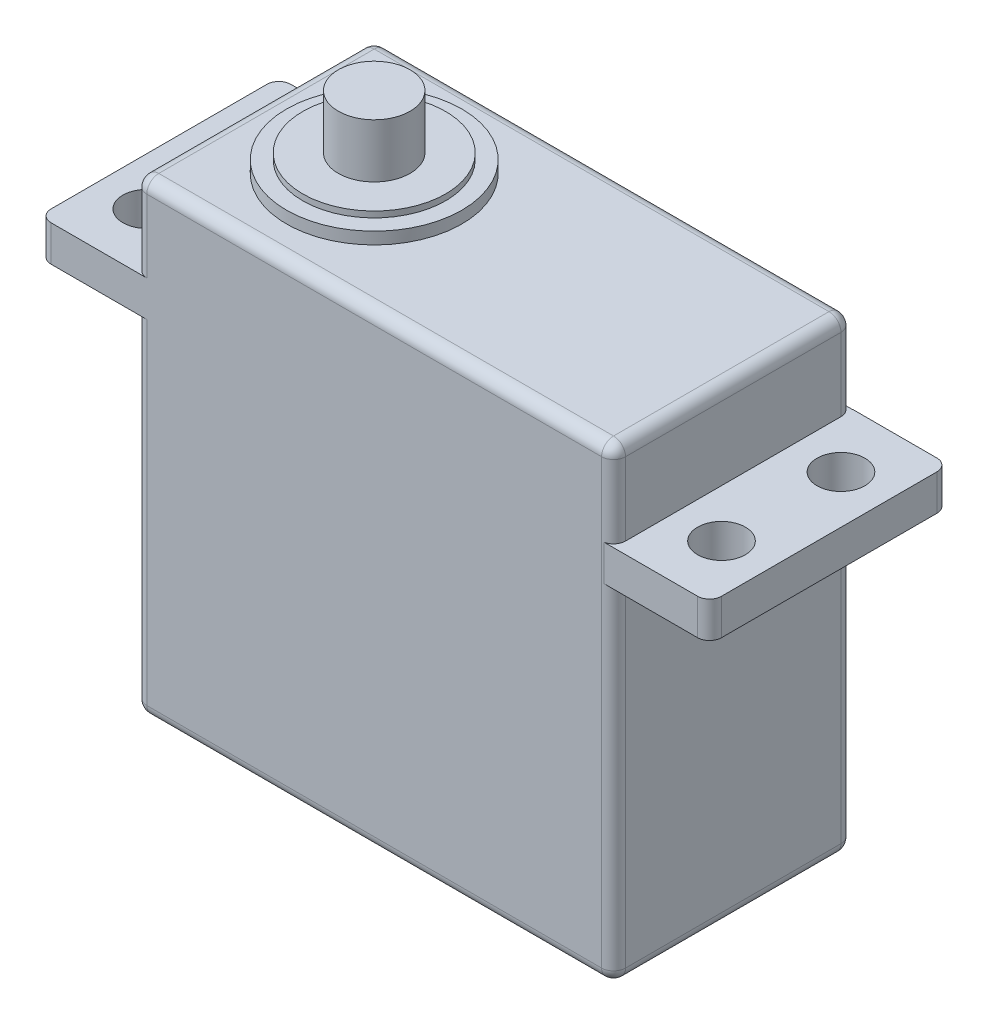
SolidWorks part; units mm, degrees
ref_plane "前视基准面" through (0, 0, 0) normal (0, 0, 1) x (1, 0, 0)
ref_plane "上视基准面" through (0, 0, 0) normal (0, 1, 0) x (1, 0, 0)
ref_plane "右视基准面" through (0, 0, 0) normal (1, 0, 0) x (0, 0, -1)
other "Configuration Table"
sketch "草图1" plane through (0, 0, 0) normal (0, 0, 1) x (1, 0, 0)
  line L1 (-23.1016, 36.7005) -> (16.8984, 36.7005)
  line L2 (-23.1016, 36.7005) -> (-23.1016, -2.2995)
  line L3 (-23.1016, -2.2995) -> (16.8984, -2.2995)
  line L4 (16.8984, 36.7005) -> (16.8984, -2.2995)
  dimension "D1" = 40
  dimension "D2" = 39
extrude "凸台-拉伸1" add sketch "草图1" along normal blind 20
sketch "草图3" plane through (16.8984, 0, 0) normal (1, 0, 0) x (0, 0, -1)
  line L3 (-19.9805, 29.5969) -> (0.0195, 29.5969)
  line L4 (-19.9805, 29.5969) -> (-19.9805, 26.5969)
  line L5 (-19.9805, 26.5969) -> (0.0195, 26.5969)
  line L6 (0.0195, 29.5969) -> (0.0195, 26.5969)
  dimension "D1" = 20
  dimension "D2" = 3
extrude "凸台-拉伸2" add sketch "草图3" along normal blind 8 contours L4 L3 L6 L5
sketch "草图6" plane through (-23.1016, 0, 0) normal (-1, 0, 0) x (0, 0, 1)
  line L0 (20, 36.7005) -> (20, -2.2995) construction
  line L1 (-0.0334, 29.6303) -> (20, 29.6303)
  line L2 (-0.0334, 29.6303) -> (-0.0334, 26.6303)
  line L3 (-0.0334, 26.6303) -> (20, 26.6303)
  line L4 (20, 29.6303) -> (20, 26.6303)
  dimension "D1" = 3
extrude "凸台-拉伸4" add sketch "草图6" along normal blind 8 contours L2 L1 L4 L3
sketch "草图7" plane through (0, 0, 0) normal (0, 1, 0) x (1, 0, 0)
  circle A1 centre (-27.1016, -15) radius 2
  circle B0 centre (-27.1016, -4.9666) radius 2
sketch_block_instance "块1-1"
sketch_block "块1"
extrude "切除-拉伸1" cut sketch "草图7" against normal blind 50 and the other way blind 38
sketch "草图8" plane through (0, 29.5969, 0) normal (0, 1, 0) x (1, 0, 0)
  circle A0 centre (20.8984, -5) radius 2
  circle A1 centre (20.8984, -14.9805) radius 2
extrude "切除-拉伸2" cut sketch "草图8" against normal blind 50
sketch "草图9" plane through (0, 36.7005, 0) normal (0, 1, 0) x (1, 0, 0)
  line L0 (-23.1016, -10) -> (-13.1016, -10)
  line L1 (-23.1016, -20) -> (-23.1016, 0) construction
  circle A0 centre (-13.1016, -10) radius 3
  circle A1 centre (-13.1016, -10) radius 1.5
  circle A2 centre (-13.1016, -10) radius 5.9909
  circle A3 centre (-13.1016, -10) radius 7.3551
extrude "凸台-拉伸7" add sketch "草图9" along normal blind 6 contours A0
sketch "草图11" plane through (0, 36.7005, 0) normal (0, 1, 0) x (1, 0, 0)
  circle A0 centre (-13.1016, -10) radius 5.9706
extrude "凸台-拉伸8" add sketch "草图11" along normal blind 1.5 contours A0
sketch "草图12" plane through (0, 36.7005, 0) normal (0, 1, 0) x (1, 0, 0)
  circle A0 centre (-13.1016, -10) radius 7.3256
extrude "凸台-拉伸9" add sketch "草图12" along normal blind 1
fillet "圆角3" radius 1 3 edges at (16.8984, 36.7005, 10) (16.8984, 17.2005, 20) (-3.1016, 36.7005, 20)
fillet "圆角4" radius 1 7 edges at (16.6055, -2.2995, 19.7071) (-23.1016, 12.1654, 0) (16.8984, -2.2995, 9.5) (-3.1016, -2.2995, 0) (-23.1016, -2.2995, 10) (-3.6016, -2.2995, 20) (-23.1016, 12.1654, 20)
fillet "圆角5" radius 1 9 edges at (16.6055, -2.0066, 0.2929) (16.6055, 36.4076, 0) (-23.1016, 36.4076, 19.7071) (16.8984, 12.6487, 0) (16.8984, 32.6487, 0) (-3.6016, 36.7005, 0) (-23.1016, 33.1654, 0) (-23.1016, 36.7005, 9.5) (-23.1016, 32.6654, 20)
fillet "圆角8" radius 1 2 edges at (24.8984, 28.0969, -0.0195) (24.8984, 28.0969, 19.9805)
fillet "圆角9" radius 1 2 edges at (-31.1016, 28.1303, -0.0334) (-31.1016, 28.1303, 20)
